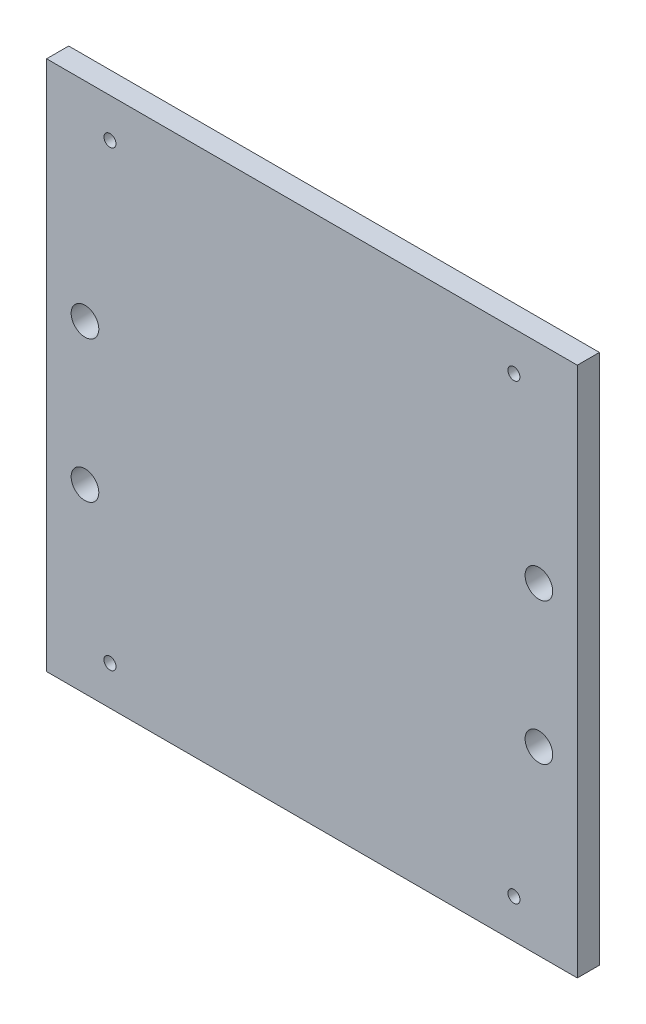
SolidWorks part; units mm, degrees
material "6061-T6 (SS)"
ref_plane "Front Plane" through (0, 0, 0) normal (0, 0, 1) x (1, 0, 0)
ref_plane "Top Plane" through (0, 0, 0) normal (0, 1, 0) x (1, 0, 0)
ref_plane "Right Plane" through (0, 0, 0) normal (1, 0, 0) x (0, 0, -1)
sketch "Sketch1" plane through (0, 0, 0) normal (0, 0, 1) x (1, 0, 0)
  line L0 (0, 187.525) -> (0, 38.475) construction
  line L1 (-67.525, 187.525) -> (67.525, 187.525) construction
  line L2 (-67.525, 187.525) -> (-67.525, 38.475) construction
  line L3 (-67.525, 38.475) -> (67.525, 38.475) construction
  line L4 (67.525, 187.525) -> (67.525, 38.475) construction
  line L6 (-76.2, 36.8) -> (76.2, 36.8)
  line L7 (-76.2, 36.8) -> (-76.2, 189.2)
  line L8 (-76.2, 189.2) -> (76.2, 189.2)
  line L9 (76.2, 36.8) -> (76.2, 189.2)
  line L10 (-76.2, 36.8) -> (76.2, 189.2) construction
  line L11 (-76.2, 189.2) -> (76.2, 36.8) construction
  circle A0 centre (-58, 178) radius 3 construction
  circle A1 centre (58, 48) radius 3 construction
  point P10 (0, 113)
  point P15 (0, 187.525)
  dimension "D2" = 9.525
  dimension "D3" = 9.525
  dimension "D4" = 9.525
  dimension "D1" = 9.525
  dimension "D5" = 152.4
  dimension "D6" = 152.4
extrude "Boss-Extrude1" add sketch "Sketch1" along normal blind 6.35
hole_wizard "5/16 (0.3125) Diameter Hole1" positions "Sketch2" profile "Sketch3" hole size "5/16" standard "ANSI Inch" end condition up to next
sketch "Sketch2" plane through (0, 0, 0) normal (0, 0, -1) x (-1, 0, 0)
  line L1 (0, 189.2) -> (0, 36.8) construction
  line L3 (76.2, 36.8) -> (-76.2, 36.8) construction
  line L5 (-76.2, 189.2) -> (76.2, 189.2) construction
  circle A0 centre (65.1764, 88.807) radius 2.5527 construction
  circle A1 centre (65.1764, 129.447) radius 2.5527 construction
  point P0 (65.1764, 88.807)
  point P2 (65.1764, 129.447)
  point P24 (0, 36.8)
  point P30 (0, 189.2)
  point P31 (-65.1764, 129.447)
  point P32 (-65.1764, 88.807)
sketch "Sketch3" plane through (-65.1764, 88.807, 0) normal (1, 0, 0) x (0, 1, 0)
  line L0 (0, 0) -> (0, 6.35)
  line L1 (0, 6.35) -> (3.9687, 6.35)
  line L2 (3.9687, 6.35) -> (3.9687, 0)
  line L5 (3.9687, 0) -> (0, 0)
  line L11 (0, -6.35) -> (0, 107.95) construction
  dimension "Thru Hole Dia." = 7.9375
  dimension "Thru Hole Depth" = 6.35
hole_wizard "#8-32 Tapped Hole1" positions "Sketch4" profile "Sketch5" tap size "#8-32" standard "ANSI Inch" end condition up to next
sketch "Sketch4" plane through (0, 0, 0) normal (0, 0, -1) x (-1, 0, 0)
  point P0 (-58, 178)
  point P3 (58, 178)
  point P6 (58, 48)
  point P9 (-58, 48)
sketch "Sketch5" plane through (58, 178, 0) normal (1, 0, 0) x (0, 1, 0)
  line L0 (0, 0) -> (0, 6.35)
  line L1 (0, 6.35) -> (1.7272, 6.35)
  line L2 (1.7272, 6.35) -> (1.7272, 0)
  line L5 (1.7272, 0) -> (0, 0)
  line L11 (0, -6.35) -> (0, 107.95) construction
  dimension "Thru Tap Drill Dia." = 3.4544
  dimension "Thru Tap Drill Depth" = 6.35
cosmetic thread "Hole Thread1"
cosmetic thread "Hole Thread2"
cosmetic thread "Hole Thread3"
cosmetic thread "Hole Thread4"
